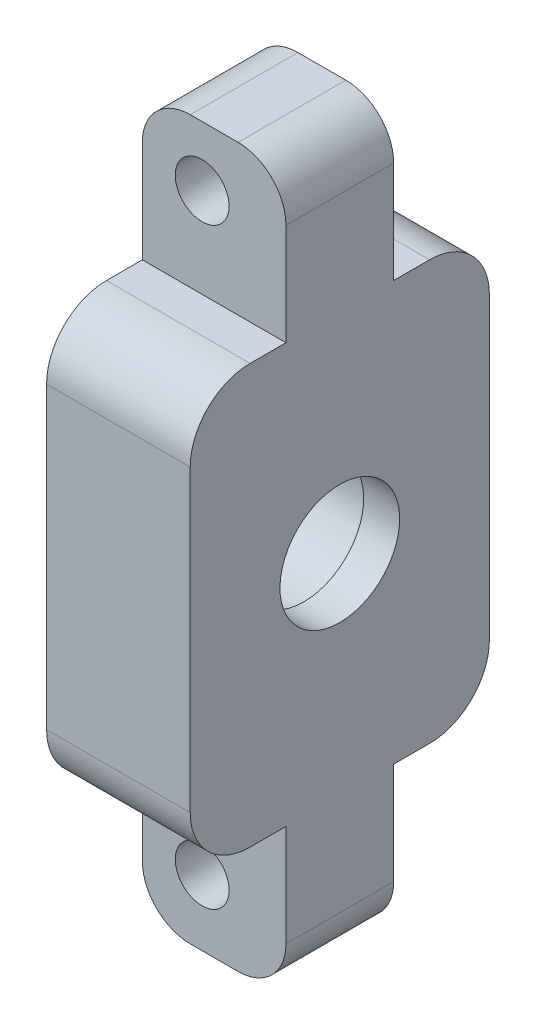
SolidWorks part; units mm, degrees
ref_plane "Front Plane" through (0, 0, 0) normal (0, 0, 1) x (1, 0, 0)
ref_plane "Top Plane" through (0, 0, 0) normal (0, 1, 0) x (1, 0, 0)
ref_plane "Right Plane" through (0, 0, 0) normal (1, 0, 0) x (0, 0, -1)
sketch "Sketch2" plane through (0, 0, 0) normal (0, 0, 1) x (1, 0, 0)
  line L1 (-6, 30) -> (6, 30)
  line L2 (-6, 30) -> (-6, -30)
  line L3 (-6, -30) -> (6, -30)
  line L4 (6, 30) -> (6, -30)
  line L5 (-6, 30) -> (6, -30) construction
  line L6 (-6, -30) -> (6, 30) construction
  point P0 (0, 0)
  dimension "D1" = 60
  dimension "D2" = 12
extrude "Boss-Extrude1" add sketch "Sketch2" along normal mid plane 25
sketch "Sketch3" plane through (6, 0, 0) normal (1, 0, 0) x (0, 0, -1)
  line L0 (-12.5, 30) -> (12.5, 30) construction
  line L2 (-4.5, 30) -> (-4.5, 17.5)
  line L4 (4.5, 30) -> (4.5, 17.5)
  line L9 (55, 0) -> (-55, 0) construction
  line L10 (-12.5, 30) -> (-4.5, 30)
  line L11 (-12.5, 30) -> (-12.5, 17.5)
  line L12 (-12.5, 17.5) -> (-4.5, 17.5)
  line L13 (-4.5, 30) -> (-4.5, 17.5)
  line L14 (12.5, 30) -> (4.5, 30)
  line L15 (12.5, 30) -> (12.5, 17.5)
  line L16 (12.5, 17.5) -> (4.5, 17.5)
  line L17 (4.5, 30) -> (4.5, 17.5)
  line L18 (4.5, -30) -> (4.5, -17.5)
  line L19 (12.5, -17.5) -> (4.5, -17.5)
  line L20 (12.5, -30) -> (12.5, -17.5)
  line L21 (12.5, -30) -> (4.5, -30)
  line L22 (-4.5, -30) -> (-4.5, -17.5)
  line L23 (-12.5, -17.5) -> (-4.5, -17.5)
  line L24 (-12.5, -30) -> (-12.5, -17.5)
  line L25 (-12.5, -30) -> (-4.5, -30)
  line L26 (4.5, -30) -> (4.5, -17.5)
  line L27 (-4.5, -30) -> (-4.5, -17.5)
  line M4 (12.5, -30) -> (12.5, 30)
  line M5 (12.5, 30) -> (-12.5, 30)
  line M6 (-12.5, 30) -> (-12.5, -30)
  line M7 (-12.5, -30) -> (12.5, -30)
  dimension "D1" = 9
extrude "Cut-Extrude1" cut sketch "Sketch3" against normal through all contours L23 L22 M6 M7 | L19 L18 M4 M7 | L16 L4 M4 M5 | L12 L2 M6 M5 region at (6, 23.75, 8.5) region at (6, 23.75, -8.5) region at (6, -23.75, 8.5) region at (6, -23.75, -8.5)
sketch "Sketch4" plane through (0, 0, 4.5) normal (0, 0, 1) x (1, 0, 0)
  line L0 (-6, -30) -> (6, -30) construction
  line L1 (-6, 30) -> (-6, 17.5) construction
  line L2 (-6, -30) -> (-6, -17.5) construction
  circle A0 centre (-1, 25) radius 2.25
  circle A1 centre (-1, -24.5) radius 2.25
  dimension "D1" = 4.5
  dimension "D2" = 4.5
  dimension "D3" = 49.5
  dimension "D4" = 5.5
  dimension "D5" = 5
  dimension "D6" = 5
extrude "Cut-Extrude2" cut sketch "Sketch4" against normal through all
fillet "Fillet1" radius 5 4 edges at (0, -17.5, 12.5) (0, -17.5, -12.5) (0, 17.5, -12.5) (0, 17.5, 12.5)
fillet "Fillet2" radius 4 4 edges at (6, -30, 0) (-6, -30, 0) (-6, 30, 0) (6, 30, 0)
sketch "Sketch5" plane through (-6, 0, 0) normal (-1, 0, 0) x (0, 0, 1)
  circle A0 centre (0, 0) radius 5
  dimension "D1" = 10
extrude "Cut-Extrude3" cut sketch "Sketch5" against normal blind 4 from offset 8 offset against normal yes
sketch "Sketch6" plane through (-6, 0, 0) normal (-1, 0, 0) x (0, 0, 1)
  circle A0 centre (0, 0) radius 7.5
  dimension "D1" = 15
extrude "Cut-Extrude4" cut sketch "Sketch6" against normal blind 4
sketch "Sketch8" plane through (-2, 0, 0) normal (-1, 0, 0) x (0, 0, 1)
  circle A0 centre (0, 0) radius 5.5
  dimension "D1" = 11
extrude "Cut-Extrude6" cut sketch "Sketch8" against normal blind 5
